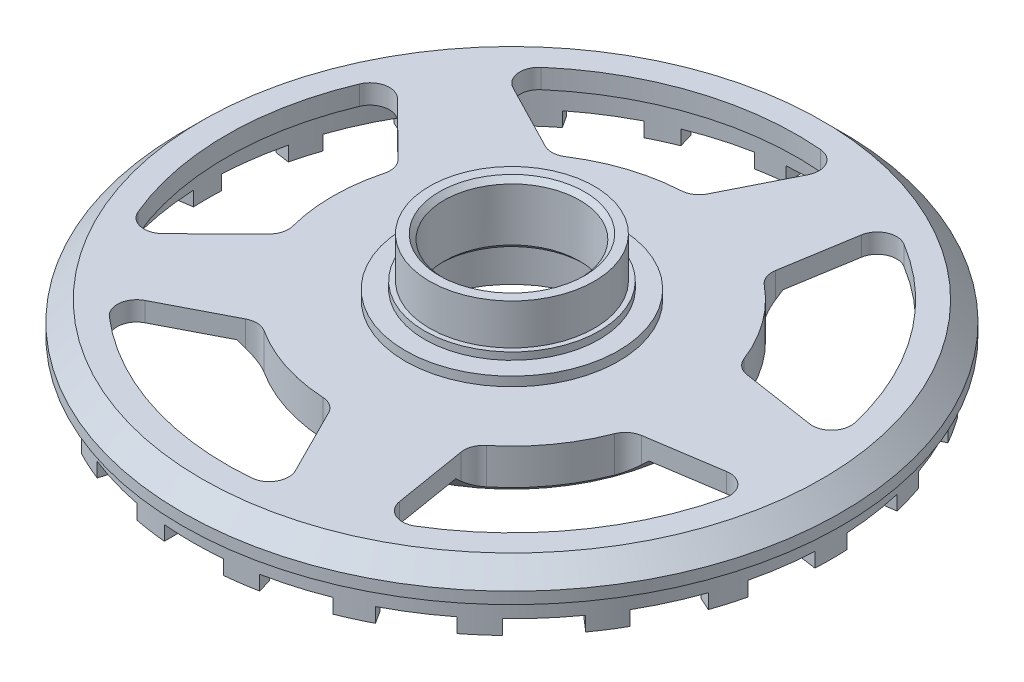
SolidWorks part; units mm, degrees
ref_plane "Front Plane" through (0, 0, 0) normal (0, 0, 1) x (1, 0, 0)
ref_plane "Top Plane" through (0, 0, 0) normal (0, 1, 0) x (1, 0, 0)
ref_plane "Right Plane" through (0, 0, 0) normal (1, 0, 0) x (0, 0, -1)
ref_axis "Axis1" through (0, 0, 0) along (0, 1, 0)
sketch "Sketch1" plane through (0, 0, 0) normal (0, 0, 1) x (1, 0, 0)
  line L0 (-32.95, 8) -> (-32.95, 4.5)
  line L2 (-32.95, 4.5) -> (-31.45, 4.5)
  line L3 (-31.45, 4.5) -> (-31.45, 8.2)
  line L4 (-32.95, 8) -> (-34, 8)
  line L5 (-34, 8) -> (-34, 8.5)
  line L7 (-11, 12.15) -> (-9, 12.15)
  line L8 (-9, 12.15) -> (-9, 12.9)
  line L9 (-9, 12.9) -> (-8.5, 12.9)
  line L10 (-8.5, 12.9) -> (-8.5, 17.1)
  line L11 (-8.5, 17.1) -> (-7, 17.1)
  line L12 (-7, 17.1) -> (-7, 10.65)
  line L15 (0, 0) -> (0, -50000) construction
  line L16 (-30.45, 9.2) -> (-31.45, 8.2)
  line L18 (-10.5, 10.15) -> (-10.5, 5.15)
  line L21 (-7, 10.65) -> (-9.5, 10.65)
  line L26 (-10.5, 10.15) -> (-9.5, 10.15)
  line L27 (-9.5, 10.15) -> (-9.5, 10.65)
  line L29 (-20.2, 9.2) -> (-30.45, 9.2)
  line L32 (-34, 9.2) -> (-34, 8.5)
  line L34 (-32, 11.2) -> (-11, 11.2)
  line L35 (-34, 9.2) -> (-32, 11.2)
  line L36 (-11, 12.15) -> (-11, 11.2)
  line L38 (19.25, 6) -> (-19.25, 6) construction
  line L39 (-20.2, 9.2) -> (-18, 7)
  line L40 (-18, 7) -> (-12, 7)
  line L41 (-12, 7) -> (-12, 5.15)
  line L42 (-12, 5.15) -> (-10.5, 5.15)
  line L43 (7.5467, 2.15) -> (-7.5467, 2.15) construction
  point P6 (-31.45, 9.2)
  point P19 (-34, 11.2)
  dimension "D1" = 3.5
  dimension "D2" = 1.5
  dimension "D3" = 17
  dimension "D4" = 4.2
  dimension "D5" = 0.75
  dimension "D6" = 0.5
  dimension "D7" = 1.5
  dimension "D8" = 1.5
  dimension "D9" = 0.5
  dimension "D10" = 65.9
  dimension "D11" = 22
  dimension "D12" = 21
  dimension "D13" = 1.5
  dimension "D14" = 1
  dimension "D15" = 5
  dimension "D16" = 3
  dimension "D17" = 6
  dimension "D18" = 0.5
  dimension "D19" = 2
  dimension "D20" = 3.2
  dimension "D21" = 1
  dimension "D22" = 135
revolve "Revolve1" add sketch "Sketch1" angle 360 about L15
sketch "Sketch2" plane through (0, 0, 0) normal (0, 0, 1) x (1, 0, 0)
  line L1 (-3.05, -0.7629) -> (3.05, -0.7629)
  line L2 (-3.05, -0.7629) -> (-3.05, 6)
  line L3 (-3.05, 6) -> (3.05, 6)
  line L4 (3.05, -0.7629) -> (3.05, 6)
  line L5 (-32.95, 8) -> (32.95, 8) construction
  point P4 (0, -0.7629)
  dimension "D1" = 6.1
  dimension "D2" = 2
extrude "Cut-Extrude2" cut sketch "Sketch2" along normal through all from offset 20
pattern_circular "CirPattern1" count 22 over 360 about axis through (0, 0, 0) along (0, 1, 0) of "Cut-Extrude2"
sketch "Sketch4" plane through (0, 0, 0) normal (0, 1, 0) x (1, 0, 0)
  circle A0 centre (-15.5, 0) radius 2.06
  dimension "D1" = 4.12
  dimension "D2" = 15.5
extrude "Cut-Extrude3" cut sketch "Sketch4" along normal blind 3 from surface starting at face at (0, 7, 12)
pattern_circular "CirPattern2" count 24 over 360 about axis through (0, 0, 0) along (0, 1, 0) of "Cut-Extrude3"
sketch "Sketch5" plane through (0, 0, 0) normal (0, 1, 0) x (1, 0, 0)
  circle A0 centre (0, 0) radius 15.5
extrude "Cut-Extrude-Thin1" cut sketch "Sketch5" along normal up to surface (10 mm away) thin up to face at (0, 10, 0) thin type mid plane wall 2
chamfer "Chamfer1" distance 0.5 angle 45 2 edges at (0, 17.1, 7) (0, 10.65, 7)
sketch "Sketch6" plane through (0, 0, 0) normal (0, 1, 0) x (1, 0, 0)
  line L0 (0, 0) -> (-50000, 0) construction
  line L1 (-25.8825, -14.0499) -> (-17.5608, -5.8198)
  line L2 (-17.5608, 5.8198) -> (-25.8825, 14.0499)
  arc A0 (-25.8825, -14.0499) -> (-25.8825, 14.0499) centre (0, 0) cw
  arc A1 (-17.5608, -5.8198) -> (-17.5608, 5.8198) centre (0, 0) cw
  circle A2 centre (0, 0) radius 30.45 construction
  point P9 (-29.45, 0)
  point P10 (-18.5, 0)
  dimension "D1" = 1
extrude "Cut-Extrude4" cut sketch "Sketch6" along normal through all
fillet "Fillet1" radius 2 4 edges at (-25.8825, 10.2, 14.0499) (-17.5608, 9.35, 5.8198) (-17.5608, 9.35, -5.8198) (-25.8825, 10.2, -14.0499)
pattern_circular "CirPattern3" count 5 over 360 about axis through (0, 0, 0) along (0, 1, 0) of "Cut-Extrude4", "Fillet1"
